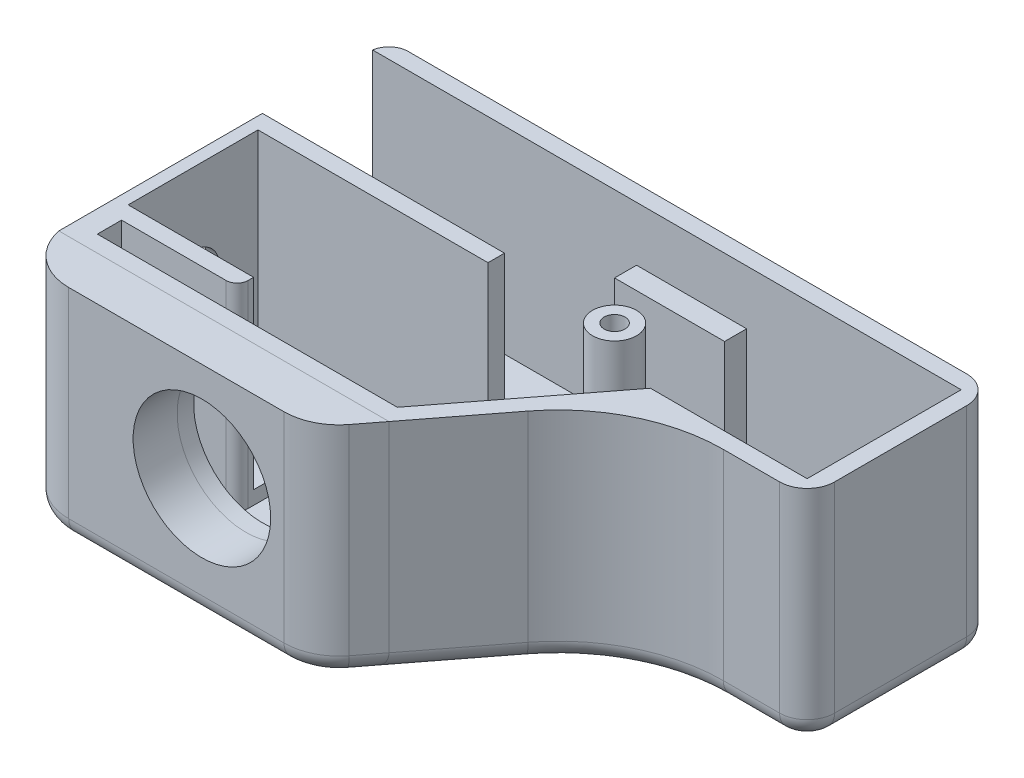
SolidWorks part; units mm, degrees
ref_plane "Front Plane" through (0, 0, 0) normal (0, 0, 1) x (1, 0, 0)
ref_plane "Top Plane" through (0, 0, 0) normal (0, 1, 0) x (1, 0, 0)
ref_plane "Right Plane" through (0, 0, 0) normal (1, 0, 0) x (0, 0, -1)
sketch "Sketch1" plane through (0, 0, 0) normal (0, 1, 0) x (1, 0, 0)
  line L5 (0, 0) -> (69.85, 0)
  line L6 (69.85, 0) -> (69.85, -21.59)
  line L7 (69.85, -21.59) -> (50.8, -21.59)
  line L8 (50.8, -21.59) -> (38.1, -38.1)
  line L9 (38.1, -38.1) -> (0, -38.1)
  line L10 (0, -38.1) -> (0, 0)
  dimension "D1" = 38.1
  dimension "D2" = 38.1
  dimension "D3" = 69.85
  dimension "D4" = 21.59
  dimension "D5" = 19.05
extrude "Boss-Extrude1" add sketch "Sketch1" along normal blind 2.54
sketch "Sketch2" plane through (0, 2.54, 0) normal (0, 1, 0) x (1, 0, 0)
  line L0 (0, 0) -> (0, -1.905)
  line L1 (0, 0) -> (0, -38.1) construction
  line L2 (0, -1.905) -> (67.945, -1.905)
  line L3 (67.945, -1.905) -> (67.945, -19.685)
  line L4 (67.945, -19.685) -> (49.862, -19.685)
  line L5 (49.862, -19.685) -> (37.162, -36.195)
  line L6 (37.162, -36.195) -> (0, -36.195)
  line L7 (0, -36.195) -> (0, -38.1)
  line L8 (0, -38.1) -> (38.1, -38.1)
  line L9 (38.1, -38.1) -> (50.8, -21.59)
  line L10 (50.8, -21.59) -> (69.85, -21.59)
  line L11 (69.85, -21.59) -> (69.85, 0)
  line L12 (69.85, 0) -> (0, 0)
  dimension "D1" = 1.905
  dimension "D2" = 1.905
  dimension "D3" = 1.905
  dimension "D4" = 1.905
  dimension "D5" = 1.905
extrude "Boss-Extrude2" add sketch "Sketch2" along normal blind 22.7965
sketch "Sketch3" plane through (0, 2.54, 0) normal (0, 1, 0) x (1, 0, 0)
  line L0 (0, -1.905) -> (0, -36.195) construction
  line L1 (0, -16.51) -> (27.94, -16.51)
  line L2 (0, -16.51) -> (0, -14.605)
  line L3 (0, -14.605) -> (27.94, -14.605)
  line L4 (27.94, -16.51) -> (27.94, -14.605)
  line L6 (0, -1.905) -> (67.945, -1.905) construction
  line L8 (0, -31.496) -> (15.875, -31.496)
  line L9 (0, -31.496) -> (0, -33.401)
  line L10 (0, -33.401) -> (15.875, -33.401)
  line L11 (15.875, -31.496) -> (15.875, -33.401)
  dimension "D1" = 12.7
  dimension "D2" = 1.905
  dimension "D3" = 27.94
  dimension "D4" = 14.986
  dimension "D5" = 1.905
  dimension "D6" = 15.875
extrude "Boss-Extrude3" add sketch "Sketch3" along normal blind 22.7965
sketch "Sketch4" plane through (0, 0, 0) normal (-1, 0, 0) x (0, 0, 1)
  line L0 (34.798, 25.3365) -> (34.798, 2.54) construction
  line L1 (33.401, 25.3365) -> (36.195, 25.3365)
  line L2 (33.401, 25.3365) -> (33.401, 2.54)
  line L3 (33.401, 2.54) -> (36.195, 2.54)
  line L4 (36.195, 25.3365) -> (36.195, 2.54)
  line L5 (33.401, 13.9383) -> (36.195, 13.9383) construction
  line L7 (35.6235, 16.1608) -> (33.9725, 16.1608)
  line L8 (35.6235, 16.1608) -> (35.6235, 11.7157)
  line L9 (35.6235, 11.7157) -> (33.9725, 11.7157)
  line L10 (33.9725, 16.1608) -> (33.9725, 11.7157)
  line L11 (35.6235, 16.1608) -> (33.9725, 11.7157) construction
  line L12 (35.6235, 11.7157) -> (33.9725, 16.1608) construction
  point P10 (34.798, 13.9383)
  point P15 (33.5926, 15.2082)
  point P16 (36.0395, 15.2082)
  dimension "D1" = 1.651
  dimension "D2" = 4.445
  dimension "D3" = 11.3983
extrude "Boss-Extrude4" add sketch "Sketch4" against normal blind 2.54
fillet "Fillet5" radius 1.27 1 edges at (15.875, 13.9383, 33.401)
sketch "Sketch6" plane through (0, 25.3365, 0) normal (0, 1, 0) x (1, 0, 0)
  line L1 (0, -38.1) -> (38.1, -38.1)
  line L2 (0, -38.1) -> (0, -43.18)
  line L3 (0, -43.18) -> (38.1, -43.18)
  line L4 (38.1, -38.1) -> (38.1, -43.18)
  dimension "D1" = 5.08
extrude "Boss-Extrude5" add sketch "Sketch6" against normal up to surface (25.3365 mm away) separate body up to face at (38.1, 0, 19.8967)
sketch "Sketch7" plane through (0, 0, 43.18) normal (0, 0, 1) x (1, 0, 0)
  line L0 (38.1, 13.9383) -> (0, 13.9382) construction
  line L3 (38.1, 25.3365) -> (38.1, 0) construction
  line L4 (0, 0) -> (38.1, 0) construction
  circle A0 centre (21.59, 13.9383) radius 7.9375
  dimension "D1" = 15.875
  dimension "D2" = 16.51
  dimension "D3" = 13.9383
extrude "Cut-Extrude1" cut sketch "Sketch7" against normal up to surface (6.985 mm away) up to face at (19.851, 13.9383, 36.195)
sketch "Sketch9" plane through (0, 25.3365, 0) normal (0, 1, 0) x (1, 0, 0)
  line L0 (38.1, -38.1) -> (34.1923, -43.18)
  line L1 (0, -43.18) -> (38.1, -43.18) construction
  line L2 (34.1923, -43.18) -> (38.1, -43.18)
  line L3 (38.1, -43.18) -> (38.1, -38.1)
  line L4 (38.1, -38.1) -> (50.8, -21.59) construction
extrude "Cut-Extrude2" cut sketch "Sketch9" against normal through all
sketch "Sketch10" plane through (0, 2.54, 0) normal (0, 1, 0) x (1, 0, 0)
  line L0 (69.85, -21.59) -> (69.85, 0) construction
  line L1 (50.8, -21.59) -> (69.85, -21.59) construction
  circle A0 centre (41.275, -15.24) radius 2.54
  circle A2 centre (41.275, -15.24) radius 1.2065
  dimension "D1" = 5.08
  dimension "D2" = 2.413
  dimension "D3" = 28.575
  dimension "D4" = 6.35
extrude "Boss-Extrude6" add sketch "Sketch10" along normal up to surface (22.7965 mm away) up to face at (29.6007, 25.3365, 23.3611)
fillet "Fillet6" radius 19.05 1 edges at (50.8, 12.6682, 21.59)
fillet "Fillet7" radius 6.35 2 edges at (0, 12.6682, 43.18) (34.1923, 12.6682, 43.18)
fillet "Fillet8" radius 3.175 2 edges at (69.85, 12.6682, 21.59) (69.85, 12.6682, 0)
fillet "Fillet9" radius 2.2225 7 edges at (33.3375, 0, 0) (68.9201, 0, 0.9299) (69.85, 0, 10.795) (68.9201, 0, 20.6601) (63.4276, 0, 21.59) (41.5904, 0, 33.5625) (51.7649, 0, 23.5495)
fillet "Fillet10" radius 2.2225 4 edges at (2.2056, 0, 41.7487) (37.0994, 0, 39.4008) (33.8707, 0, 42.5268) (18.6436, 0, 43.18)
fillet "Fillet11" radius 2.2225 3 edges at (0, 13.7795, 0) (0, 0.651, 0.651) (0, 0, 20.1613)
sketch "Sketch11" plane through (0, 2.54, 0) normal (0, 1, 0) x (1, 0, 0)
  line L1 (0, -16.51) -> (15.875, -16.51)
  line L2 (0, -16.51) -> (0, -31.496)
  line L3 (0, -31.496) -> (15.875, -31.496)
  line L4 (15.875, -16.51) -> (15.875, -31.496)
extrude "Boss-Extrude7" add sketch "Sketch11" along normal blind 1.5684
sketch "Sketch12" plane through (0, 0, 0) normal (-1, 0, 0) x (0, 0, 1)
  line L0 (24.003, 25.3365) -> (24.003, 4.1084) construction
  line L1 (16.51, 25.3365) -> (31.496, 25.3365)
  line L2 (16.51, 25.3365) -> (16.51, 4.1084)
  line L3 (16.51, 4.1084) -> (31.496, 4.1084)
  line L4 (31.496, 25.3365) -> (31.496, 4.1084)
  line L5 (16.51, 13.9763) -> (31.496, 13.9764) construction
  circle A0 centre (24.003, 13.9763) radius 3.048
  point P12 (0, 0)
  point P13 (0, 0)
  dimension "D1" = 6.096
  dimension "D2" = 9.8679
extrude "Boss-Extrude8" add sketch "Sketch12" against normal blind 1.397
sketch "Sketch14" plane through (0, 0, 0) normal (0, 0, -1) x (-1, 0, 0)
  line L0 (-69.85, 13.7795) -> (-0.0228, 13.9383) construction
  line L3 (-69.85, 2.2225) -> (-69.85, 25.3365) construction
  line L5 (-0.0228, 25.3365) -> (-0.0228, 2.54) construction
  circle A0 centre (-61.468, 13.7986) radius 2.5781
  point P8 (0, 0)
  point P9 (-57.6588, 15.1589)
  dimension "D1" = 5.1562
  dimension "D2" = 8.382
extrude "Cut-Extrude3" cut sketch "Sketch14" against normal up to surface (1.905 mm away) up to face at (33.9839, 13.9383, 1.905)
sketch "Sketch15" plane through (0, 2.54, 0) normal (0, 1, 0) x (1, 0, 0)
  line L0 (27.94, -16.51) -> (27.94, -14.605) construction
  line L1 (34.29, -5.715) -> (46.99, -5.715)
  line L2 (34.29, -5.715) -> (34.29, -8.255)
  line L3 (34.29, -8.255) -> (46.99, -8.255)
  line L4 (46.99, -5.715) -> (46.99, -8.255)
  line L5 (0.0228, -1.905) -> (67.945, -1.905) construction
  point P4 (34.29, -6.985)
  dimension "D1" = 12.7
  dimension "D2" = 2.54
  dimension "D3" = 6.35
  dimension "D4" = 3.81
extrude "Boss-Extrude9" add sketch "Sketch15" along normal blind 20.32
sketch "Sketch16" plane through (0, 4.1084, 0) normal (0, 1, 0) x (1, 0, 0)
  line L0 (15.875, -16.51) -> (1.397, -16.51) construction
  line L1 (10.795, -21.59) -> (20.447, -21.59)
  line L2 (10.795, -21.59) -> (10.795, -26.543)
  line L3 (10.795, -26.543) -> (20.447, -26.543)
  line L4 (20.447, -21.59) -> (20.447, -26.543)
  line L5 (15.875, -31.496) -> (15.875, -16.51) construction
  dimension "D1" = 5.08
  dimension "D2" = 4.953
  dimension "D3" = 9.652
  dimension "D4" = 5.08
extrude "Cut-Extrude4" cut sketch "Sketch16" against normal blind 3.556
